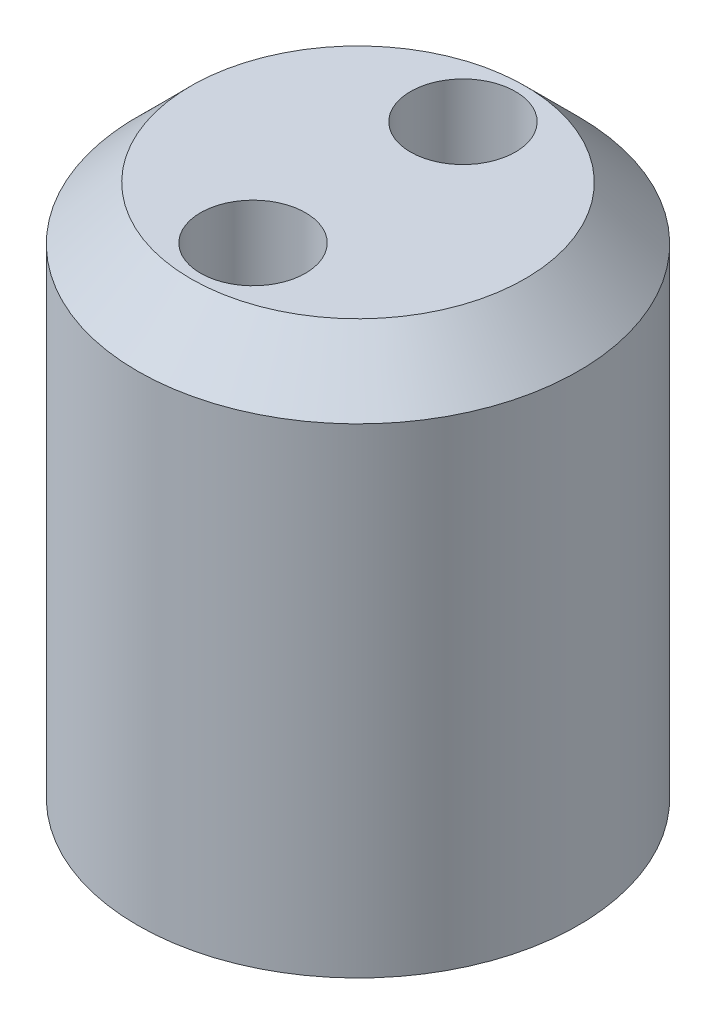
SolidWorks part; units mm, degrees
ref_plane "Front Plane" through (0, 0, 0) normal (0, 0, 1) x (1, 0, 0)
ref_plane "Top Plane" through (0, 0, 0) normal (0, 1, 0) x (1, 0, 0)
ref_plane "Right Plane" through (0, 0, 0) normal (1, 0, 0) x (0, 0, -1)
sketch "Sketch1" plane through (0, 0, 0) normal (0, 1, 0) x (1, 0, 0)
  line L0 (0, -5) -> (0, 5) construction
  circle A0 centre (0, 0) radius 10.5
  circle A2 centre (0, 5) radius 2.5
  circle A3 centre (0, -5) radius 2.5
  dimension "D1" = 21
  dimension "D2" = 5
  dimension "D3" = 10
extrude "Boss-Extrude1" add sketch "Sketch1" along normal blind 25.4
chamfer "Chamfer1" distance 2.54 angle 45 1 edges at (0, 25.4, 10.5)
equation "\"cf_tube_outer_diameter\"= 25mm"
equation "\"cf_tube_inner_diameter\" = 21mm"
equation "\"mid_plate_mid_to_top\" = 100mm"
equation "\"mid_plate_mid_to_bottom\" = 30mm"
equation "\"mid_plate_horizontal_spacing\"=250mm"
equation "\"cf_plate_thickness\" =4mm"
equation "\"mid_tube_length\" = 500mm"
equation "\"D1@Sketch1\"=\"cf_tube_inner_diameter\""
